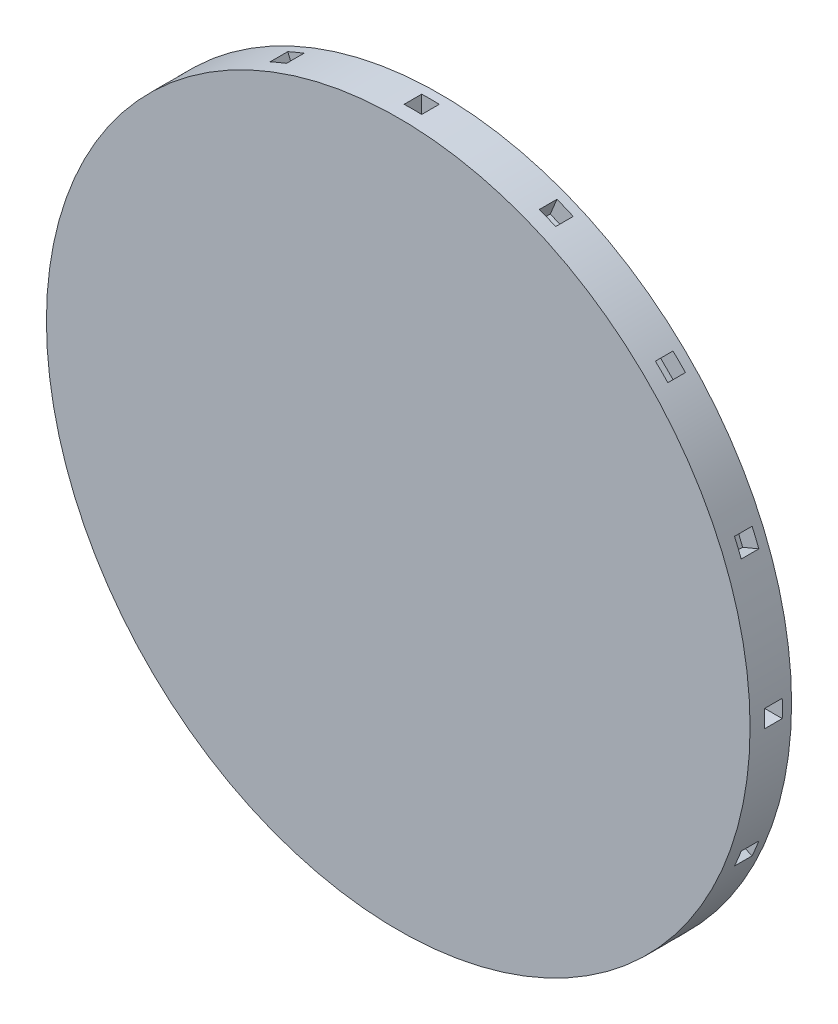
SolidWorks part; units mm, degrees
ref_plane "Front Plane" through (0, 0, 0) normal (1, 0, 0) x (0, 1, 0)
ref_plane "Top Plane" through (0, 0, 0) normal (0, 0, 1) x (0, 1, 0)
ref_plane "Right Plane" through (0, 0, 0) normal (0, 1, 0) x (-1, 0, 0)
sketch "Sketch1" plane through (0, 0, 0) normal (1, 0, 0) x (0, 1, 0)
  line L0 (0, 0) -> (-152.4, 0)
  line L1 (-152.4, 0) -> (-152.4, -6.35)
  line L2 (-152.4, -6.35) -> (-139.7, -6.35)
  line L3 (-139.7, -6.35) -> (-139.7, -13.97)
  line L4 (-139.7, -13.97) -> (-152.4, -13.97)
  line L5 (-152.4, -13.97) -> (-152.4, -17.97)
  line L6 (-152.4, -17.97) -> (-88.9, -17.97)
  line L8 (-88.9, -23.97) -> (-101.6, -30.32)
  line L9 (-101.6, -30.32) -> (0, -30.32)
  line L10 (0, -30.32) -> (0, 0) construction
  line L11 (-88.9, -17.97) -> (-88.9, -23.97)
  line L12 (0, 0) -> (0, -30.32)
  dimension "D1" = 152.4
  dimension "D2" = 6.35
  dimension "D3" = 7.62
  dimension "D4" = 12.7
  dimension "D5" = 4
  dimension "D6" = 63.5
  dimension "D7" = 6
  dimension "D8" = 101.6
  dimension "D9" = 6.35
revolve "Revolve1" add sketch "Sketch1" angle 360 about L10
sketch "Sketch2" plane through (0, 0, 0) normal (0, 0, 1) x (1, 0, 0)
  line L0 (-3.81, 152.3524) -> (-3.81, 144.78)
  line L1 (-3.81, 144.78) -> (3.81, 144.78)
  line L2 (3.81, 144.78) -> (3.81, 152.3524)
  line L3 (58.9249, 132.3013) -> (61.8227, 139.2972)
  line L4 (51.8849, 135.2173) -> (58.9249, 132.3013)
  line L5 (54.7827, 142.2133) -> (51.8849, 135.2173)
  line L6 (105.069, 99.6808) -> (110.4235, 105.0353)
  line L7 (99.6808, 105.069) -> (105.069, 99.6808)
  line L8 (105.0353, 110.4235) -> (99.6808, 105.069)
  line L9 (135.2173, 51.8849) -> (142.2133, 54.7827)
  line L10 (132.3013, 58.9249) -> (135.2173, 51.8849)
  line L11 (139.2972, 61.8227) -> (132.3013, 58.9249)
  line L12 (144.78, -3.81) -> (152.3524, -3.81)
  line L13 (144.78, 3.81) -> (144.78, -3.81)
  line L14 (152.3524, 3.81) -> (144.78, 3.81)
  line L15 (132.3013, -58.9249) -> (139.2972, -61.8227)
  line L16 (135.2173, -51.8849) -> (132.3013, -58.9249)
  line L17 (142.2133, -54.7827) -> (135.2173, -51.8849)
  line L18 (99.6808, -105.069) -> (105.0353, -110.4235)
  line L19 (105.069, -99.6808) -> (99.6808, -105.069)
  line L20 (110.4235, -105.0353) -> (105.069, -99.6808)
  line L21 (51.8849, -135.2173) -> (54.7827, -142.2133)
  line L22 (58.9249, -132.3013) -> (51.8849, -135.2173)
  line L23 (61.8227, -139.2972) -> (58.9249, -132.3013)
  line L24 (-3.81, -144.78) -> (-3.81, -152.3524)
  line L25 (3.81, -144.78) -> (-3.81, -144.78)
  line L26 (3.81, -152.3524) -> (3.81, -144.78)
  line L27 (-58.9249, -132.3013) -> (-61.8227, -139.2972)
  line L28 (-51.8849, -135.2173) -> (-58.9249, -132.3013)
  line L29 (-54.7827, -142.2133) -> (-51.8849, -135.2173)
  line L30 (-105.069, -99.6808) -> (-110.4235, -105.0353)
  line L31 (-99.6808, -105.069) -> (-105.069, -99.6808)
  line L32 (-105.0353, -110.4235) -> (-99.6808, -105.069)
  line L33 (-135.2173, -51.8849) -> (-142.2133, -54.7827)
  line L34 (-132.3013, -58.9249) -> (-135.2173, -51.8849)
  line L35 (-139.2972, -61.8227) -> (-132.3013, -58.9249)
  line L36 (-144.78, 3.81) -> (-152.3524, 3.81)
  line L37 (-144.78, -3.81) -> (-144.78, 3.81)
  line L38 (-152.3524, -3.81) -> (-144.78, -3.81)
  line L39 (-132.3013, 58.9249) -> (-139.2972, 61.8227)
  line L40 (-135.2173, 51.8849) -> (-132.3013, 58.9249)
  line L41 (-142.2133, 54.7827) -> (-135.2173, 51.8849)
  line L42 (-99.6808, 105.069) -> (-105.0353, 110.4235)
  line L43 (-105.069, 99.6808) -> (-99.6808, 105.069)
  line L44 (-110.4235, 105.0353) -> (-105.069, 99.6808)
  line L45 (-51.8849, 135.2173) -> (-54.7827, 142.2133)
  line L46 (-58.9249, 132.3013) -> (-51.8849, 135.2173)
  line L47 (-61.8227, 139.2972) -> (-58.9249, 132.3013)
  circle A0 centre (0, 0) radius 152.4 construction
  circle A1 centre (0, 0) radius 152.4
  point P69 (0, 0)
  circle M3 centre (0, 0) radius 152.4
  dimension "D3" = 7.62
  dimension "D1" = 3.81
  dimension "D2" = 7.62
  dimension "D4" = 16
extrude "Boss-Extrude1" add sketch "Sketch2" against normal up to surface (17.97 mm away) contours L47 L42 L43 L44 L39 L40 L41 L36 L37 L38 L33 L34 L35 L30 L31 L32 L27 L28 L29 L24 L25 L26 L21 L22 L23 L18 L19 L20 L15 L16 L17 L12 L13 L14 L9 L10 L11 L6 M3 region at (0, 0, 0) up to face at (-88.9, 0, -17.97)
